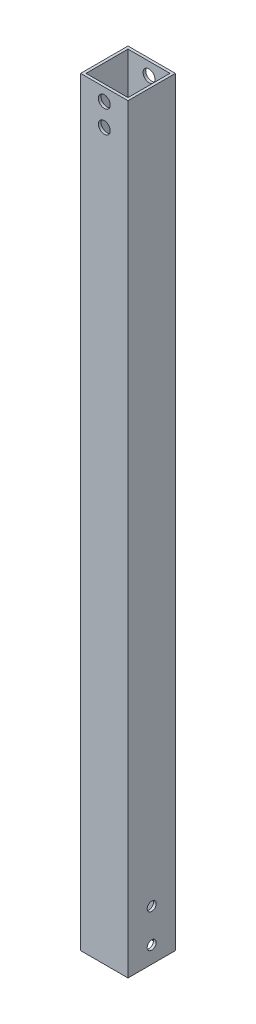
SolidWorks part; units mm, degrees
material "6061 Alloy"
ref_plane "Front Plane" through (0, 0, 0) normal (0, 0, 1) x (1, 0, 0)
ref_plane "Top Plane" through (0, 0, 0) normal (0, 1, 0) x (1, 0, 0)
ref_plane "Right Plane" through (0, 0, 0) normal (1, 0, 0) x (0, 0, -1)
sketch "Sketch1" plane through (0, 0, 0) normal (0, 1, 0) x (1, 0, 0)
  line L9 (12.7, -12.7) -> (-12.7, -12.7)
  line L10 (12.7, -12.7) -> (12.7, 12.7)
  line L11 (12.7, 12.7) -> (-12.7, 12.7)
  line L12 (-12.7, -12.7) -> (-12.7, 12.7)
  line L13 (12.7, -12.7) -> (-12.7, 12.7) construction
  line L14 (12.7, 12.7) -> (-12.7, -12.7) construction
  point P0 (0, 0)
  dimension "D1" = 25.4
extrude "Extrude-Thin1" add sketch "Sketch1" along normal blind 431.8 thin thin type mid plane wall 1.524
hole_wizard "1/4 Clearance Hole1" positions "Sketch2" profile "Sketch3" hole size "1/4" standard "ANSI Inch" end condition through all
sketch "Sketch2" plane through (0, 0, -13.462) normal (0, 0, -1) x (-1, 0, 0)
  point P0 (0, 424.6245)
  point P3 (0, 411.9245)
sketch "Sketch3" plane through (0, 424.6245, -13.462) normal (1, 0, 0) x (0, 1, 0)
  line L0 (0, 0) -> (0, 26.924)
  line L1 (0, 26.924) -> (3.3782, 26.924)
  line L2 (3.3782, 26.924) -> (3.3782, 0)
  line L5 (3.3782, 0) -> (0, 0)
  line L11 (0, -6.35) -> (0, 107.95) construction
  dimension "Thru Hole Dia." = 6.7564
  dimension "Thru Hole Depth" = 26.924
sketch "Sketch4" plane through (13.462, 0, 0) normal (1, 0, 0) x (0, 0, -1)
  line L0 (-13.462, 0) -> (13.462, 0) construction
  circle A0 centre (0, 9.525) radius 2.54
  circle A1 centre (0, 28.575) radius 2.54
  dimension "D1" = 5.08
  dimension "D2" = 9.525
  dimension "D3" = 28.575
hole_wizard "#10 Clearance Hole1" positions "Sketch5" profile "Sketch6" hole size "#10" standard "ANSI Inch" end condition through all
sketch "Sketch5" plane through (13.462, 0, 0) normal (1, 0, 0) x (0, 0, -1)
  point P0 (0, 9.525)
  point P3 (0, 28.575)
sketch "Sketch6" plane through (13.462, 9.525, 0) normal (0, 1, 0) x (0, 0, -1)
  line L0 (0, 0) -> (0, 26.924)
  line L1 (0, 26.924) -> (2.5527, 26.924)
  line L2 (2.5527, 26.924) -> (2.5527, 0)
  line L5 (2.5527, 0) -> (0, 0)
  line L11 (0, -6.35) -> (0, 107.95) construction
  dimension "Thru Hole Dia." = 5.1054
  dimension "Thru Hole Depth" = 26.924
